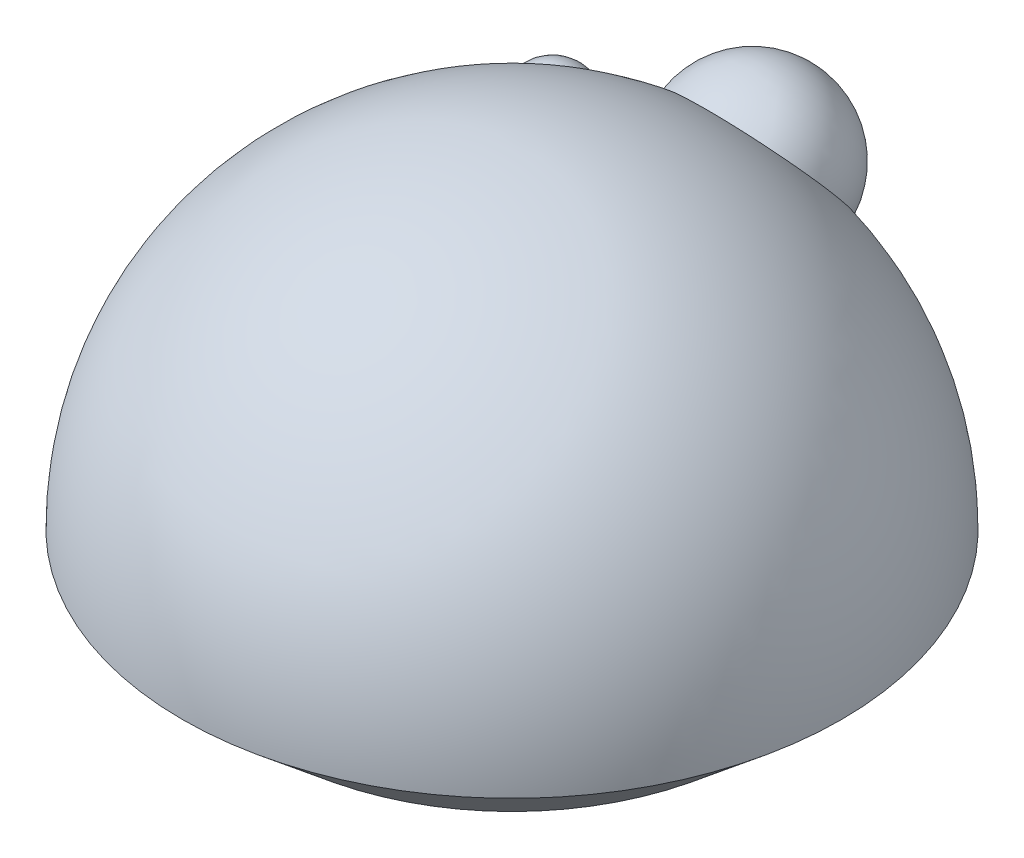
SolidWorks part; units mm, degrees
ref_plane "前视基准面" through (0, 0, 0) normal (0, 0, 1) x (1, 0, 0)
ref_plane "上视基准面" through (0, 0, 0) normal (0, 1, 0) x (1, 0, 0)
ref_plane "右视基准面" through (0, 0, 0) normal (1, 0, 0) x (0, 0, -1)
sketch "草图2" plane through (0, 0, 0) normal (0, 0, 1) x (1, 0, 0)
  line L0 (-257.1955, 151.2049) -> (-7.1955, 151.2049) construction
sketch "草图1" plane through (0, 0, 0) normal (0, 0, 1) x (1, 0, 0)
  line L0 (0, 213.0813) -> (0, 125) construction
  line L1 (-75, 129.2321) -> (-54.8019, 112.3466)
  line L3 (0, 204.2321) -> (0, 125)
  line L4 (0, 112.3466) -> (0, -92.4675) construction
  arc A0 (0, 204.2321) -> (-75, 129.2321) centre (0, 129.2321) ccw
  arc A2 (125, 0) -> (-125, 0) centre (0, 0) ccw construction
  arc A3 (0, 125) -> (-54.8019, 112.3466) centre (0, 0) ccw
  dimension "D1" = 150
revolve "旋转1" add sketch "草图1" angle 360 about L0
sketch "草图4" plane through (0, 0, 0) normal (0, 0, 1) x (1, 0, 0)
  line L0 (-267.5655, 157.0579) -> (-17.5655, 157.0579) construction
sketch "草图5" plane through (0, 0, 0) normal (0, 0, 1) x (1, 0, 0)
  circle A0 centre (-7.2257, 174.3995) radius 18.3327
sketch "草图6" plane through (0, 0, 0) normal (1, 0, 0) x (0, 0, -1)
  line L0 (0, 174.3995) -> (91.3481, 174.3995) construction
  line L2 (0, 192.7321) -> (0, 156.0668) construction
  line L3 (36.2297, 174.3995) -> (73.2297, 174.3995)
  arc A1 (73.2297, 174.3995) -> (36.2297, 174.3995) centre (54.7297, 174.3995) ccw
  dimension "D1" = 37
revolve "旋转2" add sketch "草图6" angle 360 about L0
sketch "草图7" plane through (0, 0, 0) normal (0, 0, 1) x (1, 0, 0)
  line L0 (0, 0) -> (0, 263.5649)
ref_plane "基准面1" through (0, 0, 0) normal (-0.7665, 0, 0.6422) x (0, 1, 0)
sketch "草图9" plane through (0, 0, 0) normal (-0.7665, 0, 0.6422) x (0, 1, 0)
  line L0 (156.5562, 65.8792) -> (163.2588, 82.0394)
  line L1 (129.2321, 0) -> (163.2588, 82.0394) construction
  line L2 (129.2321, 75) -> (129.2321, -75) construction
  line L3 (156.5562, 65.8792) -> (148.4761, 69.2305)
  line L4 (148.4761, 69.2305) -> (151.8274, 77.3106)
  arc A1 (163.2588, 82.0394) -> (151.8274, 77.3106) centre (159.9075, 73.9593) ccw
revolve "旋转4" add sketch "草图9" angle 360 about L1
sketch "草图12" plane through (0, 0, 0) normal (0, 1, 0) x (1, 0, 0)
  line L0 (-327.2334, -236.6742) -> (-753.9, -236.6742) construction
sketch "草图13" plane through (0, 0, 0) normal (0, 1, 0) x (1, 0, 0)
  line L1 (-1.0269, 41.6885) -> (-1.0269, 31.6179)
  line L2 (15.4688, 41.8965) -> (11.2375, 29.5713)
  line L3 (1.0269, 41.6885) -> (1.0269, 31.6179)
  line L4 (13.5263, 42.5633) -> (9.2951, 30.2382)
  line L5 (0, 31.6346) -> (0, 44.6609) construction
  line L6 (28.2344, 34.6037) -> (20.2305, 24.3202)
  line L7 (26.6137, 35.8651) -> (18.6098, 25.5817)
  line L8 (37.9404, 23.5611) -> (27.0311, 16.4337)
  line L9 (36.8171, 25.2804) -> (25.9078, 18.153)
  line L10 (43.5349, 9.9653) -> (30.9025, 6.7663)
  line L11 (43.0308, 11.9562) -> (30.3983, 8.7572)
  line L12 (44.4118, -4.7105) -> (31.4251, -3.6344)
  line L13 (44.5814, -2.6637) -> (31.5947, -1.5876)
  line L14 (40.476, -18.8757) -> (28.5423, -13.6411)
  line L15 (41.301, -16.995) -> (29.3673, -11.7604)
  line L16 (32.1539, -30.9955) -> (22.5665, -22.1697)
  line L17 (33.5449, -29.4845) -> (23.9575, -20.6587)
  line L18 (20.3475, -39.7565) -> (14.1453, -28.2958)
  line L19 (22.1537, -38.779) -> (15.9516, -27.3184)
  line L20 (6.3361, -44.2092) -> (4.1913, -31.3557)
  line L21 (8.3619, -43.8711) -> (6.217, -31.0176)
  line L22 (-8.3619, -43.8711) -> (-6.217, -31.0176)
  line L23 (-6.3361, -44.2092) -> (-4.1913, -31.3557)
  line L24 (-22.1537, -38.779) -> (-15.9516, -27.3184)
  line L25 (-20.3475, -39.7565) -> (-14.1453, -28.2958)
  line L26 (-33.5449, -29.4845) -> (-23.9575, -20.6587)
  line L27 (-32.1539, -30.9955) -> (-22.5665, -22.1697)
  line L28 (-41.301, -16.995) -> (-29.3673, -11.7604)
  line L29 (-40.476, -18.8757) -> (-28.5423, -13.6411)
  line L30 (-44.5814, -2.6637) -> (-31.5947, -1.5876)
  line L31 (-44.4118, -4.7105) -> (-31.4251, -3.6344)
  line L32 (-43.0308, 11.9562) -> (-30.3983, 8.7572)
  line L33 (-43.5349, 9.9653) -> (-30.9025, 6.7663)
  line L34 (-36.8171, 25.2804) -> (-25.9078, 18.153)
  line L35 (-37.9404, 23.5611) -> (-27.0311, 16.4337)
  line L36 (-26.6137, 35.8651) -> (-18.6098, 25.5817)
  line L37 (-28.2344, 34.6037) -> (-20.2305, 24.3202)
  line L38 (-13.5263, 42.5633) -> (-9.2951, 30.2382)
  line L39 (-15.4688, 41.8965) -> (-11.2375, 29.5713)
  arc A0 (-11.2375, 29.5713) -> (-18.6098, 25.5817) centre (0, 0) ccw
  arc A1 (-15.4688, 41.8965) -> (-26.6137, 35.8651) centre (0, 0) ccw
  arc A2 (-20.2305, 24.3202) -> (-25.9078, 18.153) centre (0, 0) ccw
  arc A3 (-28.2344, 34.6037) -> (-36.8171, 25.2804) centre (0, 0) ccw
  arc A4 (-27.0311, 16.4337) -> (-30.3983, 8.7572) centre (0, 0) ccw
  arc A5 (-37.9404, 23.5611) -> (-43.0308, 11.9562) centre (0, 0) ccw
  arc A6 (-1.0269, 31.6179) -> (-9.2951, 30.2382) centre (0, 0) ccw
  arc A7 (-9.6546, 43.6049) -> (-13.5263, 42.5633) centre (0, 0) ccw
  arc A8 (13.5263, 42.5633) -> (9.6546, 43.6049) centre (0, 0) ccw
  arc A9 (9.2951, 30.2382) -> (1.0269, 31.6179) centre (0, 0) ccw
  arc A10 (18.6098, 25.5817) -> (11.2375, 29.5713) centre (0, 0) ccw
  arc A11 (25.9078, 18.153) -> (20.2305, 24.3202) centre (0, 0) ccw
  arc A12 (-30.9025, 6.7663) -> (-31.5947, -1.5876) centre (0, 0) ccw
  arc A13 (-31.4251, -3.6344) -> (-29.3673, -11.7604) centre (0, 0) ccw
  arc A14 (-43.5349, 9.9653) -> (-44.5814, -2.6637) centre (0, 0) ccw
  arc A15 (-44.4118, -4.7105) -> (-41.301, -16.995) centre (0, 0) ccw
  arc A16 (36.8171, 25.2804) -> (28.2344, 34.6037) centre (0, 0) ccw
  arc A17 (26.6137, 35.8651) -> (15.4688, 41.8965) centre (0, 0) ccw
  arc A18 (30.3983, 8.7572) -> (27.0311, 16.4337) centre (0, 0) ccw
  arc A19 (43.0308, 11.9562) -> (37.9404, 23.5611) centre (0, 0) ccw
  arc A20 (31.5947, -1.5876) -> (30.9025, 6.7663) centre (0, 0) ccw
  arc A21 (44.5814, -2.6637) -> (43.5349, 9.9653) centre (0, 0) ccw
  arc A22 (41.301, -16.995) -> (44.4118, -4.7105) centre (0, 0) ccw
  arc A23 (29.3673, -11.7604) -> (31.4251, -3.6344) centre (0, 0) ccw
  arc A24 (23.9575, -20.6587) -> (28.5423, -13.6411) centre (0, 0) ccw
  arc A25 (33.5449, -29.4845) -> (40.476, -18.8757) centre (0, 0) ccw
  arc A26 (15.9516, -27.3184) -> (22.5665, -22.1697) centre (0, 0) ccw
  arc A27 (22.1537, -38.779) -> (32.1539, -30.9955) centre (0, 0) ccw
  arc A28 (8.3619, -43.8711) -> (20.3475, -39.7565) centre (0, 0) ccw
  arc A29 (6.217, -31.0176) -> (14.1453, -28.2958) centre (0, 0) ccw
  arc A30 (-4.1913, -31.3557) -> (4.1913, -31.3557) centre (0, 0) ccw
  arc A31 (-6.3361, -44.2092) -> (6.3361, -44.2092) centre (0, 0) ccw
  arc A32 (-20.3475, -39.7565) -> (-8.3619, -43.8711) centre (0, 0) ccw
  arc A33 (-14.1453, -28.2958) -> (-6.217, -31.0176) centre (0, 0) ccw
  arc A34 (-22.5665, -22.1697) -> (-15.9516, -27.3184) centre (0, 0) ccw
  arc A35 (-32.1539, -30.9955) -> (-22.1537, -38.779) centre (0, 0) ccw
  arc A36 (-28.5423, -13.6411) -> (-23.9575, -20.6587) centre (0, 0) ccw
  arc A37 (-40.476, -18.8757) -> (-33.5449, -29.4845) centre (0, 0) ccw
  arc A38 (-17.1076, 48.4285) -> (17.1076, 48.4285) centre (0, 0) ccw
  arc A39 (-20.6814, 52.6029) -> (20.6814, 52.6029) centre (0, 0) ccw
  arc A40 (-20.6814, 52.6029) -> (-17.1076, 48.4285) centre (0, 66.6919) ccw
  arc A41 (-9.6546, 43.6049) -> (-1.0269, 41.6885) centre (0, 66.6919) ccw
  arc A42 (17.1076, 48.4285) -> (20.6814, 52.6029) centre (0, 66.6919) ccw
  arc A43 (1.0269, 41.6885) -> (9.6546, 43.6049) centre (0, 66.6919) ccw
  point P86 (0, 0)
  dimension "D1" = 19
sketch "草图15" plane through (0, 0, 0) normal (0, 0, 1) x (1, 0, 0)
  line L0 (0, 143.9055) -> (0, -149.7728) construction
  line L1 (0, 125) -> (0, -125)
  arc A0 (0, -125) -> (0, 125) centre (0, 0) ccw
revolve "旋转5" add sketch "草图15" angle 360 about L0
revolve "切除-旋转5" cut sketch "草图15<3>" angle 360 about L0
sketch "草图15<3>" plane through (0, 0, 0) normal (0, 0, 1) x (1, 0, 0) same geometry as "草图15"
